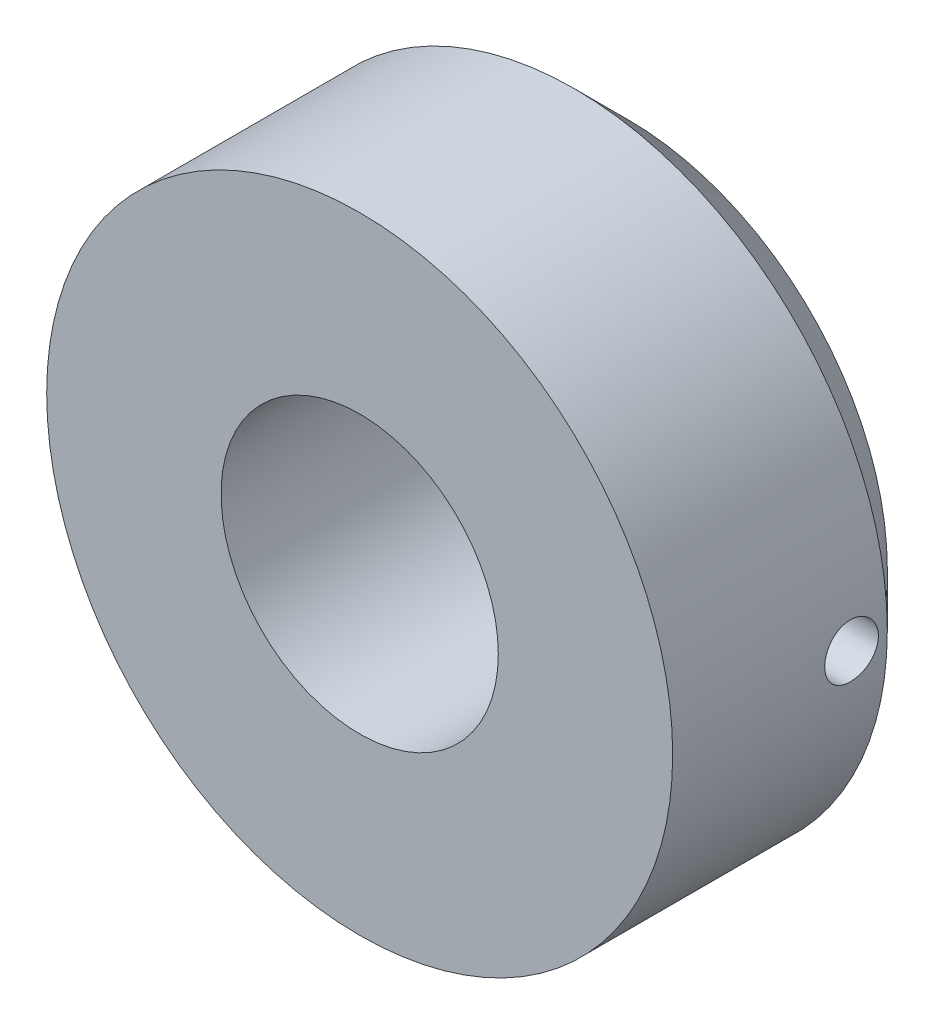
SolidWorks part; units mm, degrees
ref_plane "Front Plane" through (0, 0, 0) normal (0, 0, 1) x (1, 0, 0)
ref_plane "Top Plane" through (0, 0, 0) normal (0, 1, 0) x (1, 0, 0)
ref_plane "Right Plane" through (0, 0, 0) normal (1, 0, 0) x (0, 0, -1)
ref_axis "Z" through (0, 0, 10.75) along (0, 0, -1)
ref_axis "X" through (17.0818, 0, 0) along (-1, 0, 0)
ref_axis "Y" through (0, 19.25, 0) along (0, -1, 0)
sketch "Sketch1" plane through (0, 0, 0) normal (0, 0, 1) x (1, 0, 0)
  circle A0 centre (0, 0) radius 17.5
  circle A1 centre (0, 0) radius 8.75
  dimension "D1" = 35
  dimension "D2" = 17.5
extrude "Boss-Extrude1" add sketch "Sketch1" against normal blind 5 and the other way blind 10
sketch "Sketch2" plane through (0, 0, 0) normal (0, 1, 0) x (1, 0, 0)
  line L0 (-19.25, 0) -> (19.25, 0) construction
  line L1 (0, -8.25) -> (0, 8.25) construction
  circle A0 centre (0, 0) radius 1.5
  dimension "D1" = 3
extrude "Cut-Extrude1" cut sketch "Sketch2" against normal through all
sketch "Sketch3" plane through (0, 0, 0) normal (1, 0, 0) x (0, 0, -1)
  circle A0 centre (0, 0) radius 1.5
  dimension "D1" = 3
extrude "Cut-Extrude2" cut sketch "Sketch3" along normal through all
chamfer "Chamfer1" distance 3 angle 45 1 edges at (17.5, 0, -5)
sketch "Sketch4" plane through (0, 0, 0) normal (0, 0, 1) x (1, 0, 0)
  circle A0 centre (0, 0) radius 8.75
  circle A2 centre (0, 0) radius 8.75 construction
  circle A3 centre (0, 0) radius 7.75
  dimension "D1" = 1
extrude "Boss-Extrude2" add sketch "Sketch4" along normal up to surface and the other way up to surface up to face at (17.5, 0, 10) other way up to face at (14.5, 0, -5)
equation "\"EyeDiameter\" = 35"
equation "\"BasePlaneDistance\" = \"EyeDiameter\"/2+19.84"
equation "\"EyeClearance\" = 2"
equation "\"EyeOD\"= \"EyeDiameter\""
equation "\"D1@Sketch1\"=\"EyeOD\""
equation "\"D2@Sketch1\"=\"EyeDiameter\"*0.5"
equation "\"pinHoleDiameter\"= 3"
equation "\"D1@Sketch2\"=\"pinHoleDiameter\""
equation "\"D1@Sketch3\"=\"pinHoleDiameter\""
